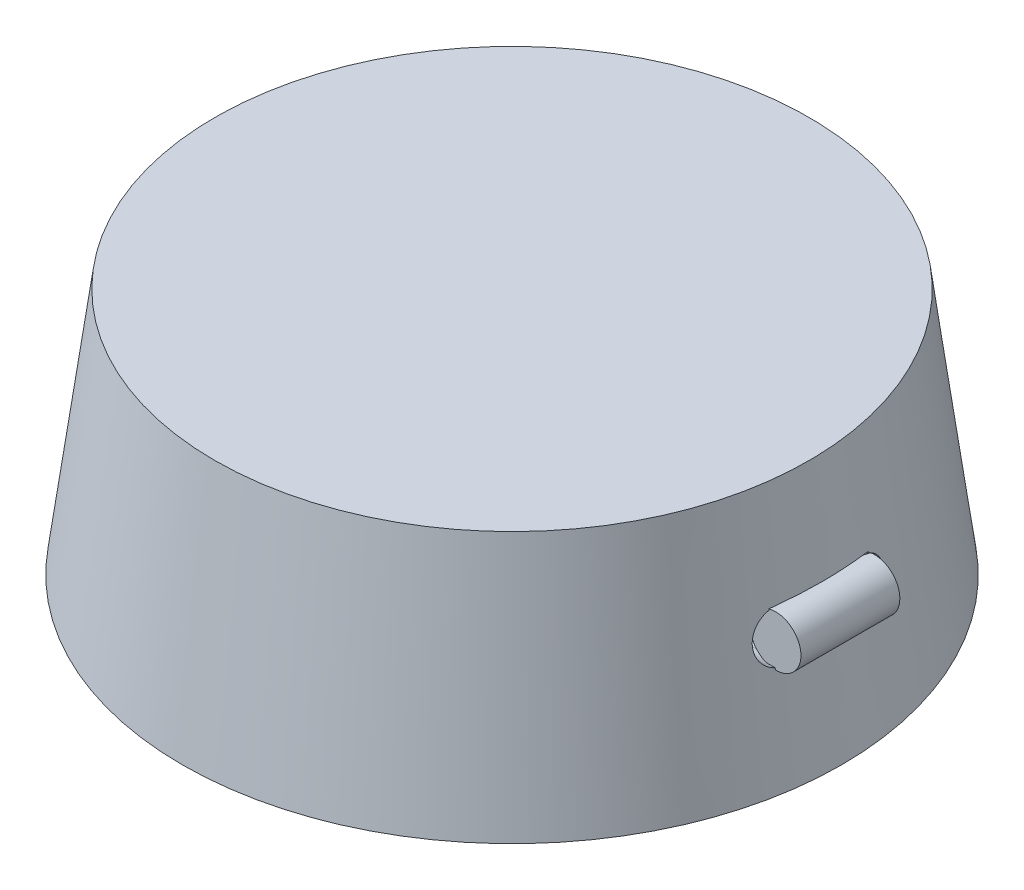
SolidWorks part; units mm, degrees
ref_plane "Front Plane" through (0, 0, 0) normal (0, 0, 1) x (1, 0, 0)
ref_plane "Top Plane" through (0, 0, 0) normal (0, 1, 0) x (1, 0, 0)
ref_plane "Right Plane" through (0, 0, 0) normal (1, 0, 0) x (0, 0, -1)
sketch "Sketch1" plane through (0, 0, 0) normal (0, 1, 0) x (1, 0, 0)
  circle A0 centre (0, 0) radius 100
  dimension "D1" = 200
extrude "Boss-Extrude1" add sketch "Sketch1" along normal blind 75 draft 7.5
sketch "Sketch2" plane through (0, 0, 0) normal (1, 0, 0) x (0, 0, -1)
  line L0 (-12.5278, 37.5) -> (12.4722, 37.5) construction
  line L1 (-12.5278, 45) -> (12.4722, 45)
  line L2 (-12.5278, 30) -> (12.4722, 30)
  arc A0 (-12.5278, 45) -> (-12.5278, 30) centre (-12.5278, 37.5) ccw
  arc A1 (12.4722, 30) -> (12.4722, 45) centre (12.4722, 37.5) ccw
  point P2 (-0.0278, 37.5)
  dimension "D1" = 15
  dimension "D2" = 25
  dimension "D3" = 37.5
extrude "Cut-Extrude1" cut sketch "Sketch2" against normal blind 122 and the other way blind 125
sketch "Sketch3" plane through (0, 0, 0) normal (0, 0, 1) x (1, 0, 0)
  circle A0 centre (94.9606, 37.5261) radius 7.6732
  point P2 (88.1673, 26.5368)
  point P3 (90.5041, 24.8676)
  point P4 (93.0939, 23.8576)
  point P5 (94.4604, 24.0161)
  point P6 (94.9555, 24.2141)
  point P7 (94.9606, 37.5261)
extrude "Boss-Extrude5" add sketch "Sketch3" along normal blind 15 and the other way blind 15
mirror "Mirror1" about plane through (0, 0, 0) normal (1, 0, 0) of "Boss-Extrude5"
sketch "Sketch5" plane through (0, 0, 0) normal (0, -1, 0) x (1, 0, 0)
  circle A0 centre (0, 0) radius 25
  dimension "D1" = 50
extrude "Cut-Extrude3" cut sketch "Sketch5" against normal blind 12.5
ref_plane "Plane1" through (0, 12.5, 0) normal (0, 1, 0) x (1, 0, 0)
sketch "Sketch6" plane through (0, 12.5, 0) normal (0, 1, 0) x (1, 0, 0)
  circle A0 centre (0, 0) radius 62.5
  dimension "D1" = 125
extrude "Cut-Extrude4" cut sketch "Sketch6" along normal blind 22.5
